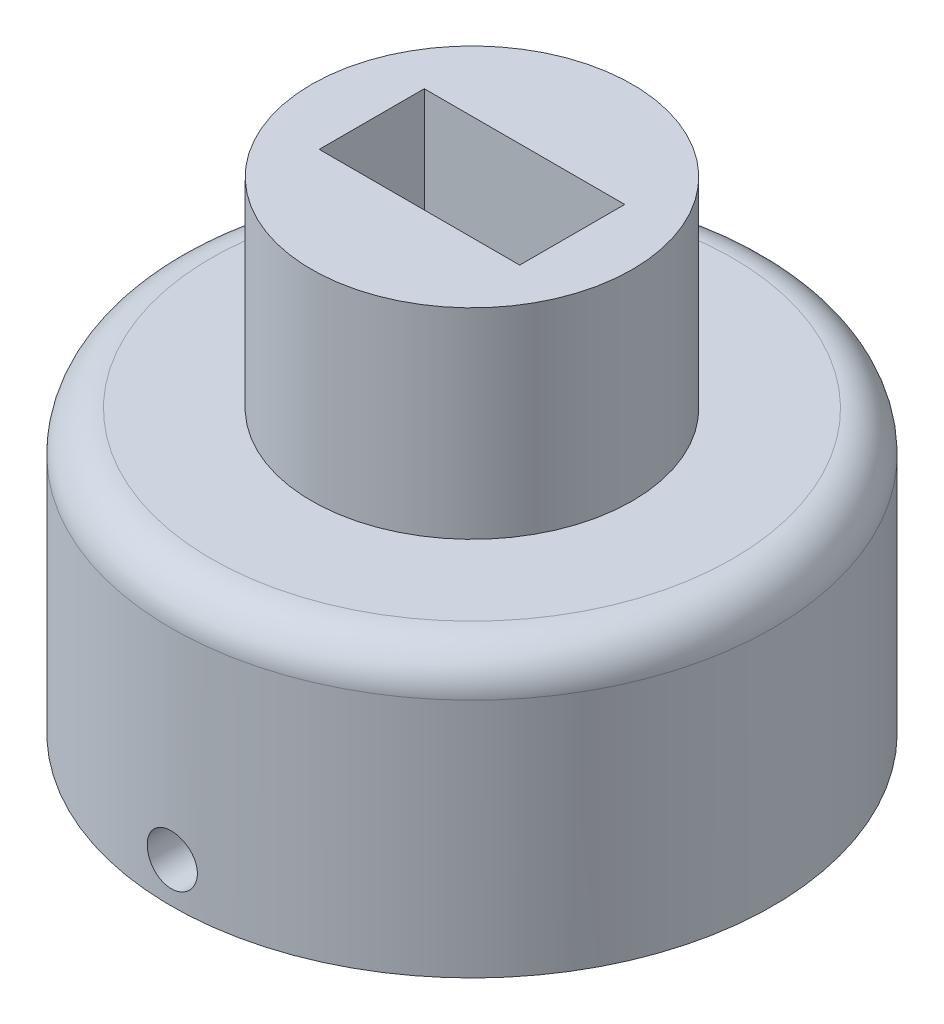
SolidWorks part; units mm, degrees
ref_plane "Front Plane" through (0, 0, 0) normal (0, 0, 1) x (1, 0, 0)
ref_plane "Top Plane" through (0, 0, 0) normal (0, 1, 0) x (1, 0, 0)
ref_plane "Right Plane" through (0, 0, 0) normal (1, 0, 0) x (0, 0, -1)
sketch "Sketch2" plane through (0, 0, 0) normal (0, 0, 1) x (1, 0, 0)
  line L0 (9.525, 0) -> (9.525, 8.89)
  line L1 (9.525, 8.89) -> (5.08, 8.89)
  line L2 (5.08, 8.89) -> (5.08, 15.24)
  line L3 (5.08, 15.24) -> (0, 15.24)
  line L4 (0, 15.24) -> (0, 0) construction
  line L5 (0, 0) -> (9.525, 0)
  line L6 (0, 15.24) -> (0, 0)
  dimension "D1" = 8.89
  dimension "D2" = 9.525
  dimension "D3" = 15.24
  dimension "D4" = 5.08
revolve "Revolve1" add sketch "Sketch2" angle 360 about L4
sketch "Sketch3" plane through (0, 0, 0) normal (0, -1, 0) x (1, 0, 0)
  line L1 (7.3323, 0) -> (3.6662, 6.35)
  line L2 (3.6662, 6.35) -> (-3.6662, 6.35)
  line L3 (-3.6662, 6.35) -> (-7.3323, 0)
  line L4 (-7.3323, 0) -> (-3.6662, -6.35)
  line L5 (-3.6662, -6.35) -> (3.6662, -6.35)
  line L6 (3.6662, -6.35) -> (7.3323, 0)
  circle A0 centre (0, 0) radius 6.35 construction
  dimension "D1" = 12.7
extrude "Cut-Extrude1" cut sketch "Sketch3" against normal blind 2.54
sketch "Sketch4" plane through (0, 15.24, 0) normal (0, 1, 0) x (1, 0, 0)
  line L1 (-3.175, -1.6637) -> (3.175, -1.6637)
  line L2 (-3.175, -1.6637) -> (-3.175, 1.6637)
  line L3 (-3.175, 1.6637) -> (3.175, 1.6637)
  line L4 (3.175, -1.6637) -> (3.175, 1.6637)
  line L5 (-3.175, -1.6637) -> (3.175, 1.6637) construction
  line L6 (-3.175, 1.6637) -> (3.175, -1.6637) construction
  point P0 (0, 0)
  dimension "D1" = 6.35
  dimension "D2" = 3.3274
extrude "Cut-Extrude2" cut sketch "Sketch4" against normal blind 7.112
sketch "Sketch5" plane through (0, 0, -6.35) normal (0, 0, 1) x (1, 0, 0)
  line L4 (-3.6662, 0) -> (3.6662, 0)
  line L5 (3.6662, 0) -> (3.6662, 2.54)
  line L6 (3.6662, 2.54) -> (-3.6662, 2.54)
  line L7 (-3.6662, 2.54) -> (-3.6662, 0)
  line L8 (-3.6662, 0) -> (3.6662, 0) construction
  line L9 (3.6662, 0) -> (3.6662, 2.54) construction
  line L10 (3.6662, 2.54) -> (-3.6662, 2.54) construction
  line L11 (-3.6662, 2.54) -> (-3.6662, 0) construction
  circle A0 centre (0, 1.27) radius 0.7937
  point P6 (0, 0)
  point P7 (-3.6662, 1.27)
  point P8 (0, 2.54)
  dimension "D2" = 1.5875
  dimension "D1" = 0
extrude "Cut-Extrude3" cut sketch "Sketch5" against normal through all both and the other way through all
fillet "Fillet2" radius 1.27 1 edges at (-9.525, 8.89, 0)
